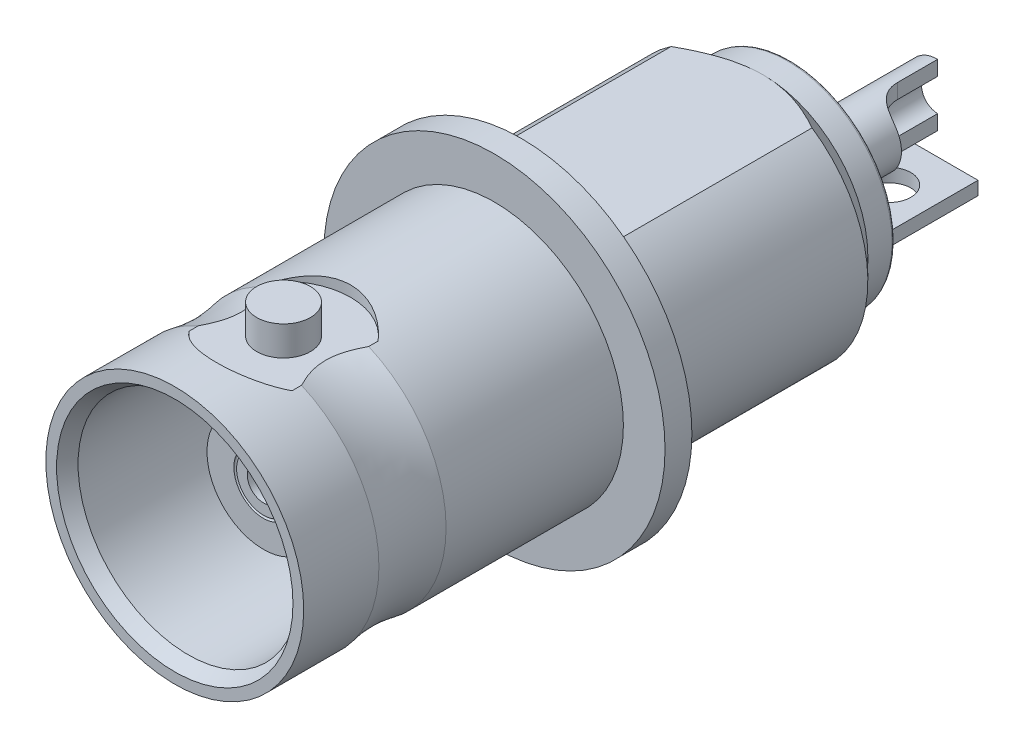
SolidWorks part; units mm, degrees
ref_plane "Спереди" through (0, 0, 0) normal (0, 0, 1) x (1, 0, 0)
ref_plane "Сверху" through (0, 0, 0) normal (0, 1, 0) x (1, 0, 0)
ref_plane "Справа" through (0, 0, 0) normal (1, 0, 0) x (0, 0, -1)
sketch "Эскиз1" plane through (0, 0, 0) normal (1, 0, 0) x (0, 0, -1)
  line L0 (0, 0) -> (94.9663, 0) construction
  line L1 (10.3, 0) -> (10.3, 0.6)
  line L2 (10.3, 0.6) -> (3.3, 0.6)
  line L3 (3.3, 0.6) -> (3.3, 1)
  line L4 (3.3, 1.1) -> (3.3, 2.1)
  line L5 (3.3, 2.1) -> (8.4, 2.1)
  line L6 (8.4, 2.1) -> (8.4, 4.1)
  line L7 (8.4, 4.1) -> (0.5, 4.1)
  line L8 (0.5, 4.1) -> (0, 4.4)
  line L9 (0, 4.4) -> (0, 4.8)
  line L10 (0, 4.8) -> (2.8, 4.8)
  line L11 (11.9, 4.8) -> (5.3, 4.8)
  line L12 (11.9, 4.8) -> (11.9, 6.35)
  line L13 (11.9, 6.35) -> (12.9, 6.35)
  line L14 (12.9, 6.35) -> (12.9, 4.7)
  line L15 (12.9, 4.7) -> (21.1, 4.7)
  line L16 (21.1, 4.7) -> (21.9, 3.9)
  line L17 (21.9, 3.9) -> (22.8, 3.9)
  line L18 (22.9, 3.8) -> (22.9, 0)
  line L19 (10.3, 0) -> (22.9, 0)
  arc A0 (3.3, 1) -> (3.3, 1.1) centre (3.3, 1.05) ccw
  arc A1 (2.8, 4.8) -> (5.3, 4.8) centre (4.05, 10.6683) ccw
  arc A2 (22.9, 3.8) -> (22.8, 3.9) centre (22.8, 3.8) ccw
  dimension "D4" = 0.05
  dimension "D13" = 9.6
  dimension "D14" = 6
  dimension "D23" = 0.1
  dimension "D1" = 1.2
  dimension "D2" = 7
  dimension "D3" = 2
  dimension "D5" = 4.2
  dimension "D6" = 5.1
  dimension "D7" = 8.4
  dimension "D8" = 0.5
  dimension "D9" = 0.3
  dimension "D10" = 9.6
  dimension "D11" = 8.2
  dimension "D12" = 11.9
  dimension "D15" = 2.5
  dimension "D16" = 2.8
  dimension "D17" = 12.7
  dimension "D18" = 1
  dimension "D19" = 9.4
  dimension "D20" = 45
  dimension "D21" = 7.8
  dimension "D22" = 10
  dimension "D24" = 1
revolve "Повернуть1" add sketch "Эскиз1" angle 360 about L0
cosmetic thread "Условное изображение резьбы1" parameters "D2"=8
sketch "Эскиз2" plane through (0, 0, -22.9) normal (0, 0, -1) x (-1, 0, 0)
  line L1 (-2.623, 3.9) -> (2.623, 3.9)
  arc A0 (-2.623, 3.9) -> (2.623, 3.9) centre (0, 0) cw
  circle A2 centre (0, 0) radius 4.7 construction
  dimension "D1" = 3.9
sketch "Эскиз3" plane through (0, 0, 0) normal (0, 1, 0) x (1, 0, 0)
  line L0 (-4.6683, 4.05) -> (4.6683, 4.05) construction
  line L1 (0, 0) -> (0, 6.6676) construction
  arc A0 (4.8, 5.3) -> (4.8, 2.8) centre (10.6683, 4.05) ccw construction
  arc A1 (-4.8, 2.8) -> (-4.8, 5.3) centre (-10.6683, 4.05) ccw construction
  circle A2 centre (0, 4.05) radius 2.5
  dimension "D1" = 5
extrude "Вытянуть2" cut sketch "Эскиз3" along normal through all from offset 4.4
extrude "Вытянуть3" cut sketch "Эскиз3<2>" against normal through all from offset 4.4 offset against normal yes
sketch "Эскиз3<2>" plane through (0, 0, 0) normal (0, 1, 0) x (1, 0, 0) same geometry as "Эскиз3"
sketch "Эскиз5" plane through (0, 0, 0) normal (0, 1, 0) x (1, 0, 0)
  circle A0 centre (0, 4.05) radius 1
  dimension "D1" = 2
extrude "Вытянуть4" add sketch "Эскиз5" along normal blind 1.1 from surface starting at face at (0.0004, 4.4, -4.0441)
extrude "Вытянуть5" add sketch "Эскиз5<2>" against normal blind 1.1 from surface starting at face at (0.0004, -4.4, -4.0441)
sketch "Эскиз5<2>" plane through (0, 0, 0) normal (0, 1, 0) x (1, 0, 0) same geometry as "Эскиз5"
extrude "Вытянуть6" cut sketch "Эскиз2" against normal up to surface (10 mm away) up to face at (6.35, 0, -12.9)
sketch "Эскиз7" plane through (0, 0, -22.9) normal (0, 0, -1) x (-1, 0, 0)
  line L1 (-1.5, -2) -> (1.5, -2)
  line L2 (-1.5, -2) -> (-1.5, -2.5)
  line L3 (-1.5, -2.5) -> (1.5, -2.5)
  line L4 (1.5, -2) -> (1.5, -2.5)
  circle A0 centre (0, 0) radius 0.6
  circle A1 centre (0, 0) radius 1.15
  dimension "D1" = 1.2
  dimension "D2" = 2.3
  dimension "D3" = 3
  dimension "D4" = 0.5
  dimension "D5" = 1.5
  dimension "D6" = 2
extrude "Вытянуть8" add sketch "Эскиз7" along normal blind 5.5
sketch "Эскиз8" plane through (0, 0, 0) normal (0, 1, 0) x (1, 0, 0)
  line L0 (3.8, 22.9) -> (-3.8, 22.9) construction
  line L1 (0, 30.6769) -> (3.4713, 30.6769)
  line L2 (0, 30.6769) -> (0, 26.9)
  line L3 (1, 25.9) -> (3.4713, 25.9)
  line L4 (3.4713, 30.6769) -> (3.4713, 25.9)
  arc A0 (1, 25.9) -> (0, 26.9) centre (1, 26.9) cw
  dimension "D1" = 1
  dimension "D2" = 3
extrude "Вытянуть9" cut sketch "Эскиз8" against normal blind 1.5 and the other way blind 1.5
sketch "Эскиз9" plane through (0, -2.5, 0) normal (0, -1, 0) x (1, 0, 0)
  line L0 (1.5, -28.4) -> (-1.5, -28.4) construction
  circle A0 centre (0, -26.6) radius 0.8
  dimension "D1" = 1.6
  dimension "D2" = 1.8
extrude "Вытянуть10" cut sketch "Эскиз9" against normal blind 1
